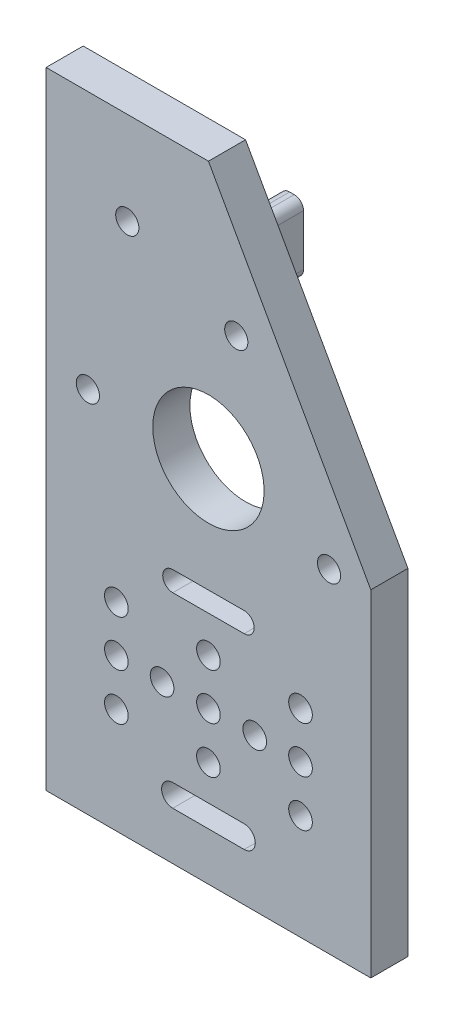
SolidWorks part; units mm, degrees
material "Plastique personnalisé"
ref_plane "Plan de face" through (0, 0, 0) normal (0, 0, 1) x (1, 0, 0)
ref_plane "Plan de dessus" through (0, 0, 0) normal (0, 1, 0) x (1, 0, 0)
ref_plane "Plan de droite" through (0, 0, 0) normal (1, 0, 0) x (0, 0, -1)
sketch "Esquisse1" plane through (0, 0, 0) normal (0, 0, 1) x (1, 0, 0)
  line L0 (0, 135) -> (35, 135) construction
  line L1 (0, 0) -> (70, 0)
  line L2 (0, 0) -> (0, 135)
  line L3 (0, 135) -> (35, 135)
  line L4 (70, 0) -> (70, 72.4723)
  line L5 (35, 135) -> (70, 72.4723) construction
  line L6 (35, 135) -> (70, 72.4723)
  line L7 (17.5, 135) -> (17.5, 115) construction
  circle A0 centre (17.5, 115) radius 2.5
  dimension "D1" = 70
  dimension "D2" = 135
  dimension "D3" = 20
extrude "Boss.-Extru.1" add sketch "Esquisse1" along normal blind 8
sketch "Esquisse3" plane through (0, 0, 0) normal (0, 0, -1) x (-1, 0, 0)
  line L0 (-35, 0) -> (-35, 38.3731) construction
  line L1 (0, 0) -> (-70, 0) construction
ref_axis "Axe1" through (35, -13.1714, 0) along (0, 1, 0)
sketch "Esquisse4" plane through (0, 0, 0) normal (0, 0, -1) x (-1, 0, 0)
  line L0 (-17.5, 115) -> (-17.5, 105) construction
  line L1 (-27.4969, 105) -> (-7.5031, 105)
  line L2 (-7.5031, 105) -> (-7.5031, 113)
  line L3 (-5.5031, 115) -> (-4.5044, 115)
  line L4 (-2.5044, 113) -> (-2.5044, 102.0044)
  line L5 (-4.5044, 100.0044) -> (-30.4956, 100.0044)
  line L6 (-32.4956, 113) -> (-32.4956, 102.0044)
  line L7 (-29.4969, 115) -> (-30.4956, 115)
  line L8 (-27.4969, 105) -> (-27.4969, 113)
  arc A0 (-29.4969, 115) -> (-27.4969, 113) centre (-29.4969, 113) cw
  arc A1 (-32.4956, 113) -> (-30.4956, 115) centre (-30.4956, 113) cw
  arc A2 (-32.4956, 102.0044) -> (-30.4956, 100.0044) centre (-30.4956, 102.0044) ccw
  arc A3 (-2.5044, 102.0044) -> (-4.5044, 100.0044) centre (-4.5044, 102.0044) cw
  arc A4 (-7.5031, 113) -> (-5.5031, 115) centre (-5.5031, 113) cw
  arc A5 (-4.5044, 115) -> (-2.5044, 113) centre (-4.5044, 113) cw
  point P9 (-17.5, 100.0044)
  point P14 (-27.4969, 115)
  point P17 (-32.4956, 115)
  point P20 (-32.4956, 100.0044)
  point P23 (-2.5044, 100.0044)
  point P26 (-7.5031, 115)
  point P29 (-2.5044, 115)
  dimension "D2" = 2
  dimension "D1" = 10
extrude "Boss.-Extru.3" add sketch "Esquisse4" along normal blind 15
fillet "Congé1" radius 1 13 edges at (27.4969, 109, 0) (28.0826, 114.4142, 0) (29.9962, 115, 0) (31.9098, 114.4142, 0) (32.4956, 107.5022, 0) (31.9098, 100.5902, 0) (17.5, 100.0044, 0) (7.5031, 109, 0) (6.9174, 114.4142, 0) (5.0038, 115, 0) (3.0902, 114.4142, 0) (2.5044, 107.5022, 0) (3.0902, 100.5902, 0)
sketch "Esquisse5" plane through (0, 0, 0) normal (0, 0, -1) x (-1, 0, 0)
  circle A0 centre (-54.85, 52.7483) radius 3.75
  circle A1 centre (-15.15, 52.7483) radius 3.75
  circle A2 centre (-54.85, 12.75) radius 3.75
  circle A3 centre (-15.15, 12.75) radius 3.75
extrude "Enlèv. mat.-Extru.1" cut sketch "Esquisse5" against normal blind 1.75
sketch "Esquisse6" plane through (0, 0, 0) normal (0, 0, -1) x (-1, 0, 0)
  circle A0 centre (-54.8469, 42.7525) radius 2.55
  circle A1 centre (-34.9977, 42.7525) radius 2.55
  circle A2 centre (-54.8469, 32.7887) radius 2.55
  circle A3 centre (-44.9846, 32.7887) radius 2.55
  circle A4 centre (-34.9977, 32.7887) radius 2.55
  circle A5 centre (-25.0004, 32.7887) radius 2.55
  circle A6 centre (-15.1504, 42.7525) radius 2.55
  circle A7 centre (-15.15, 32.7887) radius 2.55
  circle A8 centre (-15.15, 22.7468) radius 2.55
  circle A9 centre (-34.9977, 22.7468) radius 2.55
  circle A10 centre (-54.8469, 22.7468) radius 2.55
extrude "Enlèv. mat.-Extru.2" cut sketch "Esquisse6" against normal through all
sketch "Esquisse7" plane through (0, 0, 0) normal (0, 0, -1) x (-1, 0, 0)
  line L0 (-35, 55.0483) -> (-35, 50.4483) construction
  line L1 (-42.6949, 55.0483) -> (-27.3051, 55.0483) construction
  line L2 (-27.3051, 50.4483) -> (-42.6949, 50.4483) construction
  line L3 (-35, 52.7705) -> (-27.3051, 52.7483) construction
  line L4 (-42.6949, 52.7927) -> (-27.3051, 52.7483) construction
  line L5 (-42.6887, 54.9535) -> (-27.2988, 54.909)
  line L6 (-42.7012, 50.632) -> (-27.3113, 50.5876)
  line L7 (-35, 15.25) -> (-35, 10.25) construction
  line L8 (-42.6949, 15.25) -> (-27.3051, 15.25) construction
  line L9 (-27.3051, 10.25) -> (-42.6949, 10.25) construction
  line L10 (-35, 10.25) -> (-35, 12.75) construction
  line L11 (-35, 12.75) -> (-27.3051, 12.75) construction
  line L12 (-42.6949, 12.75) -> (-27.3051, 12.75) construction
  line L13 (-42.6949, 15.1528) -> (-27.3051, 15.1528)
  line L14 (-42.6949, 10.3472) -> (-27.3051, 10.3472)
  arc A0 (-42.6887, 54.9535) -> (-42.7012, 50.632) centre (-42.6949, 52.7927) ccw
  arc A1 (-27.3113, 50.5876) -> (-27.2988, 54.909) centre (-27.3051, 52.7483) ccw
  arc A2 (-42.6949, 15.1528) -> (-42.6949, 10.3472) centre (-42.6949, 12.75) ccw
  arc A3 (-27.3051, 10.3472) -> (-27.3051, 15.1528) centre (-27.3051, 12.75) ccw
  point P10 (-35, 52.7705)
  point P25 (-35, 12.75)
extrude "Enlèv. mat.-Extru.3" cut sketch "Esquisse7" against normal through all
sketch "Esquisse8" plane through (0, 0, 0) normal (0, 0, -1) x (-1, 0, 0)
  line L0 (-54.85, 61.9498) -> (-54.85, 58.9498) construction
  line L1 (-58.0962, 61.9498) -> (-51.6038, 61.9498) construction
  line L2 (-51.6038, 58.9498) -> (-58.0962, 58.9498) construction
  line L3 (-58.0962, 60.4498) -> (-51.6038, 60.4498) construction
  line L4 (-58.0962, 61.8873) -> (-51.6038, 61.8873)
  line L5 (-58.0962, 59.0123) -> (-51.6038, 59.0123)
  line L6 (-35, 65.5) -> (-35, 53.1144) construction
  line L7 (-35, 65.5) -> (-35, 0) construction
  line L8 (-11.9038, 60.4498) -> (-18.3962, 60.4498) construction
  line L9 (-11.9038, 61.8873) -> (-18.3962, 61.8873)
  line L10 (-11.9038, 59.0123) -> (-18.3962, 59.0123)
  line L11 (-54.8469, 32.7887) -> (-77.5585, 32.7887) construction
  line L12 (-58.0962, 5.1276) -> (-51.6038, 5.1276) construction
  line L13 (-58.0962, 3.6901) -> (-51.6038, 3.6901)
  line L14 (-58.0962, 6.5651) -> (-51.6038, 6.5651)
  line L15 (-11.9038, 5.1276) -> (-18.3962, 5.1276) construction
  line L16 (-11.9038, 3.6901) -> (-18.3962, 3.6901)
  line L17 (-11.9038, 6.5651) -> (-18.3962, 6.5651)
  arc A0 (-58.0962, 61.8873) -> (-58.0962, 59.0123) centre (-58.0962, 60.4498) ccw
  arc A1 (-51.6038, 59.0123) -> (-51.6038, 61.8873) centre (-51.6038, 60.4498) ccw
  arc A2 (-11.9038, 61.8873) -> (-11.9038, 59.0123) centre (-11.9038, 60.4498) cw
  arc A3 (-18.3962, 59.0123) -> (-18.3962, 61.8873) centre (-18.3962, 60.4498) cw
  arc A4 (-58.0962, 3.6901) -> (-58.0962, 6.5651) centre (-58.0962, 5.1276) cw
  arc A5 (-51.6038, 6.5651) -> (-51.6038, 3.6901) centre (-51.6038, 5.1276) cw
  arc A6 (-11.9038, 3.6901) -> (-11.9038, 6.5651) centre (-11.9038, 5.1276) ccw
  arc A7 (-18.3962, 6.5651) -> (-18.3962, 3.6901) centre (-18.3962, 5.1276) ccw
  point P8 (-54.85, 60.4498)
  point P21 (-15.15, 60.4498)
  point P31 (-54.85, 5.1276)
  point P38 (-15.15, 5.1276)
extrude "Boss.-Extru.4" add sketch "Esquisse8" along normal blind 3
fillet "Congé2" radius 0.5 16 edges at (19.8337, 5.1276, -3) (15.15, 6.5651, -3) (59.5337, 5.1276, -3) (54.85, 6.5651, -3) (19.8337, 60.4498, -3) (15.15, 61.8873, -3) (59.5337, 60.4498, -3) (54.85, 61.8873, -3) (15.15, 3.6901, -3) (10.4663, 5.1276, -3) (54.85, 3.6901, -3) (50.1663, 5.1276, -3) (15.15, 59.0123, -3) (10.4663, 60.4498, -3) (54.85, 59.0123, -3) (50.1663, 60.4498, -3)
sketch "Esquisse9" plane through (0, 0, 8) normal (0, 0, 1) x (1, 0, 0)
  line L0 (35, 0) -> (35, 163.9257) construction
  line L1 (35, -13.1714) -> (35, 38.3731) construction
ref_axis "Axe2dedans" through (35, 0, 8) along (0, 1, 0)
sketch "Esquisse10" plane through (0, 0, 0) normal (0, 0, -1) x (-1, 0, 0)
  circle A0 centre (-35, 79.4055) radius 12
  dimension "D1" = 24
extrude "Enlèv. mat.-Extru.4" cut sketch "Esquisse10" against normal through all
sketch "Esquisse11" plane through (0, 0, 0) normal (0, 0, -1) x (-1, 0, 0)
  circle A0 centre (-61, 71.8141) radius 2.5
  circle A1 centre (-9, 79.4043) radius 2.5
  circle A2 centre (-41, 105.4055) radius 2.5
extrude "Enlèv. mat.-Extru.5" cut sketch "Esquisse11" against normal through all
